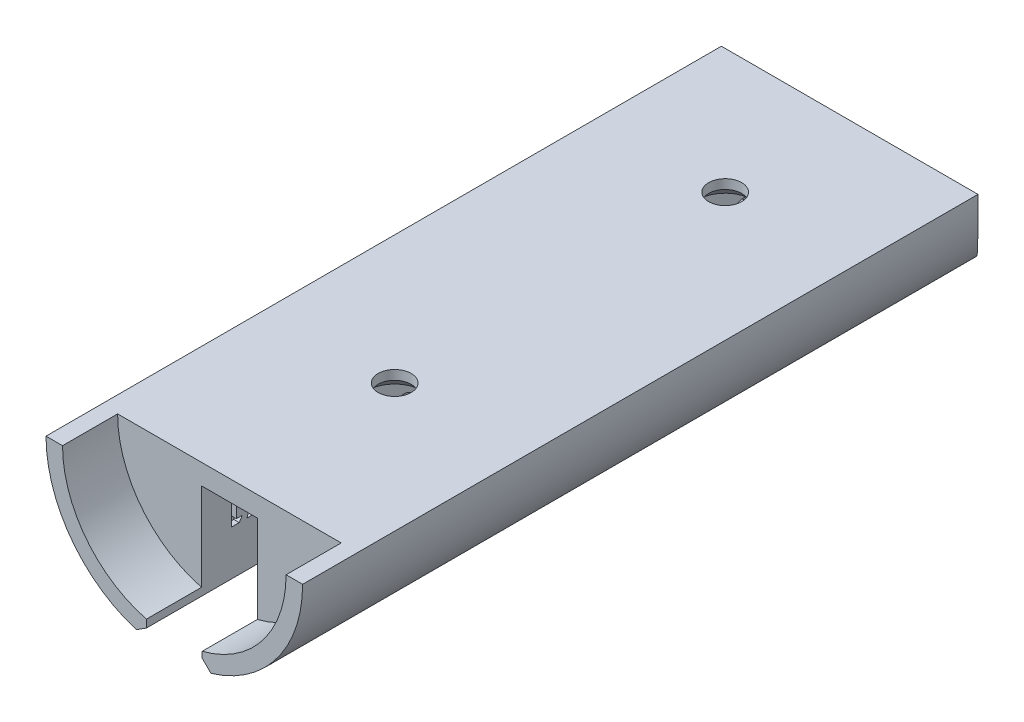
SolidWorks part; units mm, degrees
ref_plane "Front Plane" through (0, 0, 0) normal (0, 0, 1) x (1, 0, 0)
ref_plane "Top Plane" through (0, 0, 0) normal (0, 1, 0) x (1, 0, 0)
ref_plane "Right Plane" through (0, 0, 0) normal (1, 0, 0) x (0, 0, -1)
sketch "Sketch1" plane through (0, 0, 0) normal (0, 0, 1) x (1, 0, 0)
  line L1 (-14.7902, 8.509) -> (14.7902, 8.509)
  line L2 (3.0226, 5.969) -> (-3.0226, 5.969) construction
  line L11 (3.2131, -6.1595) -> (3.2131, 6.1595)
  line L12 (3.2131, 6.1595) -> (-3.2131, 6.1595)
  line L13 (-3.2131, 6.1595) -> (-3.2131, -6.1595)
  line L14 (-3.2131, -6.1595) -> (3.2131, -6.1595)
  line L15 (3.2131, -6.1595) -> (3.2131, 6.1595)
  line L16 (3.2131, 6.1595) -> (-3.2131, 6.1595)
  line L17 (-3.2131, 6.1595) -> (-3.2131, -6.1595)
  line L18 (-3.2131, -6.1595) -> (3.2131, -6.1595)
  arc A0 (-14.7902, 8.509) -> (14.7902, 8.509) centre (0, 8.509) ccw
  dimension "D1" = 2.54
  dimension "D2" = 0.1905
extrude "Boss-Extrude1" add sketch "Sketch1" along normal mid plane 190.5 contours L1 A0 L17 L16 L15 region at (0, 8.1798, 0)
sketch "Sketch2" plane through (0, 0, 95.25) normal (0, 0, 1) x (1, 0, 0)
  line L0 (-14.7902, 8.509) -> (14.7902, 8.509) construction
  line L1 (-12.8852, 8.509) -> (12.8852, 8.509)
  circle A0 centre (0, 8.509) radius 12.8852
  arc A2 (-14.7902, 8.509) -> (-3.2131, -5.9279) centre (0, 8.509) ccw construction
  line M2 (14.7902, 8.509) -> (-14.7902, 8.509)
  line M4 (-3.2131, -5.9279) -> (-3.2131, 6.1595)
  line M5 (-3.2131, 6.1595) -> (3.2131, 6.1595)
  line M6 (3.2131, 6.1595) -> (3.2131, -5.9279)
  dimension "D1" = 1.905
extrude "Cut-Extrude1" cut sketch "Sketch2" against normal blind 6.35 contours A0 M2 M4 M5 M6 region at (0, 8.2227, 95.25)
sketch "Sketch3" plane through (0, 0, -95.25) normal (0, 0, -1) x (-1, 0, 0)
  line L8 (12.8852, 8.509) -> (-12.8852, 8.509)
  line L9 (3.2131, 6.1595) -> (3.2131, -3.9691)
  line L10 (-3.2131, 6.1595) -> (3.2131, 6.1595)
  line L11 (-3.2131, -3.9691) -> (-3.2131, 6.1595)
  line L12 (12.8852, 8.509) -> (-12.8852, 8.509)
  line L13 (3.2131, 6.1595) -> (3.2131, -3.9691)
  line L14 (-3.2131, 6.1595) -> (3.2131, 6.1595)
  line L15 (-3.2131, -3.9691) -> (-3.2131, 6.1595)
  line L16 (14.7902, 8.509) -> (-14.7902, 8.509)
  line L17 (-3.2131, -5.9279) -> (-3.2131, 6.1595)
  line L18 (-3.2131, 6.1595) -> (3.2131, 6.1595)
  line L19 (3.2131, 6.1595) -> (3.2131, -5.9279)
  line L20 (14.7902, 8.509) -> (-14.7902, 8.509)
  line L21 (-3.2131, -5.9279) -> (-3.2131, 6.1595)
  line L22 (-3.2131, 6.1595) -> (3.2131, 6.1595)
  line L23 (3.2131, 6.1595) -> (3.2131, -5.9279)
  circle A2 centre (0, 8.509) radius 12.5042
  arc A4 (3.2131, -3.9691) -> (12.8852, 8.509) centre (0, 8.509) ccw
  arc A5 (-12.8852, 8.509) -> (-3.2131, -3.9691) centre (0, 8.509) ccw
  arc A6 (3.2131, -3.9691) -> (12.8852, 8.509) centre (0, 8.509) ccw
  arc A7 (-12.8852, 8.509) -> (-3.2131, -3.9691) centre (0, 8.509) ccw
  arc A9 (-14.7902, 8.509) -> (-3.2131, -5.9279) centre (0, 8.509) ccw
  arc A10 (3.2131, -5.9279) -> (14.7902, 8.509) centre (0, 8.509) ccw
  arc A11 (-14.7902, 8.509) -> (-3.2131, -5.9279) centre (0, 8.509) ccw
  arc A12 (3.2131, -5.9279) -> (14.7902, 8.509) centre (0, 8.509) ccw
  line M14 (14.7902, 8.509) -> (-14.7902, 8.509)
  arc M15 (-14.7902, 8.509) -> (-3.2131, -5.9279) centre (0, 8.509) ccw
  line M16 (-3.2131, -5.9279) -> (-3.2131, 6.1595)
  line M18 (3.2131, 6.1595) -> (3.2131, -5.9279)
  arc M19 (3.2131, -5.9279) -> (14.7902, 8.509) centre (0, 8.509) ccw
  dimension "D2" = 0.381
  dimension "D1" = 0
  dimension "D3" = 0
extrude "Cut-Extrude2" cut sketch "Sketch3" against normal blind 5.969 contours A6 M18 M19 M14 | A7 M14 M15 M16 | A7 A2 M14 M16 | L23 A6 A2 M14 region at (-10.0592, 0.7119, -95.25) region at (-13.8377, 8.3239, -95.25) region at (10.0381, 0.7912, -95.25) region at (10.3303, 0.5018, -95.25)
sketch "Sketch4" plane through (0, 6.1595, 0) normal (0, -1, 0) x (1, 0, 0)
  line L1 (0, -95.25) -> (0, 88.9) construction
  line L2 (3.2131, -95.25) -> (-3.2131, -95.25) construction
  line L3 (-3.2131, 88.9) -> (3.2131, 88.9) construction
  circle A0 centre (0, -44.45) radius 1.905
  circle A1 centre (0, 69.85) radius 1.905
  circle A2 centre (0, 31.75) radius 1.905
  point P3 (0, 29.9708)
  point P10 (0, 37.1963)
  point P11 (0, 0)
  point P15 (0, 0)
  point P16 (5.4187, -3.175)
  dimension "D1" = 3.81
  dimension "D2" = 76.2
  dimension "D3" = 38.1
  dimension "D4" = 19.05
extrude "Cut-Extrude3" cut sketch "Sketch4" against normal through all
chamfer "Chamfer1" distance 1.27 angle 45 2 edges at (3.2131, -5.9279, 2.9845) (-3.2131, -5.9279, 2.9845) first distance on face at (3.2131, -1.8282, -0.0952) first distance on face at (-10.27, 0.2734, 2.9845)
chamfer "Chamfer2" distance 1.27 angle 45 3 edges at (0, 6.1595, 71.755) (0, 6.1595, -46.355) (0, 6.1595, 29.845)
sketch "Sketch5" plane through (-3.2131, 0, 0) normal (1, 0, 0) x (0, 0, -1)
  line L0 (-3.7765, 3.6195) -> (-88.9, 3.6195) construction
  line L1 (-88.9, 6.1595) -> (95.25, 6.1595) construction
  line L2 (-88.9, -3.9691) -> (-88.9, 6.1595) construction
  text T0 "<b>Ceiling LED Mount Tee End V1  </b>" font "Century Gothic" height 3.302
  point P2 (0, 3.6195)
  point P3 (-88.9, 3.6195)
  point P10 (-3.7765, 3.6195)
  dimension "D1" = 2.54
extrude "Cut-Extrude4" cut sketch "Sketch5" against normal blind 0.635
sketch "Sketch8" plane through (0, 0, 0) normal (1, 0, 0) x (0, 0, -1)
  line L0 (-95.25, 8.509) -> (89.281, 8.509) construction
  line L1 (89.281, 8.509) -> (95.25, 8.509) construction
  line L2 (95.25, -3.5753) -> (95.25, 8.509) construction
  line L3 (89.281, -3.5753) -> (95.25, -3.5753) construction
  line L4 (89.281, -5.666) -> (89.281, 8.509) construction
  line L5 (-95.25, -5.666) -> (89.281, -5.666) construction
  line L6 (89.281, 8.509) -> (95.25, 8.509)
  line L7 (95.25, -3.5753) -> (95.25, 8.509)
  line L8 (89.281, -3.5753) -> (95.25, -3.5753)
  line L9 (89.281, -5.666) -> (89.281, -3.5753)
  line L10 (-2.2334, -5.666) -> (89.281, -5.666)
  line L11 (-16.4084, 8.509) -> (89.281, 8.509)
  line L12 (-88.9, -3.9691) -> (-88.9, 6.1595) construction
  arc A0 (-16.4084, 8.509) -> (-2.2334, -5.666) centre (-2.2334, 8.509) ccw
  circle A1 centre (-2.2334, 8.509) radius 15.1638
  dimension "D2" = 30.3276
  dimension "D1" = 72.4916
extrude "Cut-Extrude7" cut sketch "Sketch8" against normal through all both and the other way through all contours A1 L10 L9 L8 L7 L6 L11 | L10 A1 L11 A0 | L11 A1 L10 A0 region at (0, 1.3636, -52.2972) region at (0, 2.3579, 1.6193) region at (0, 13.8233, 2.764)
